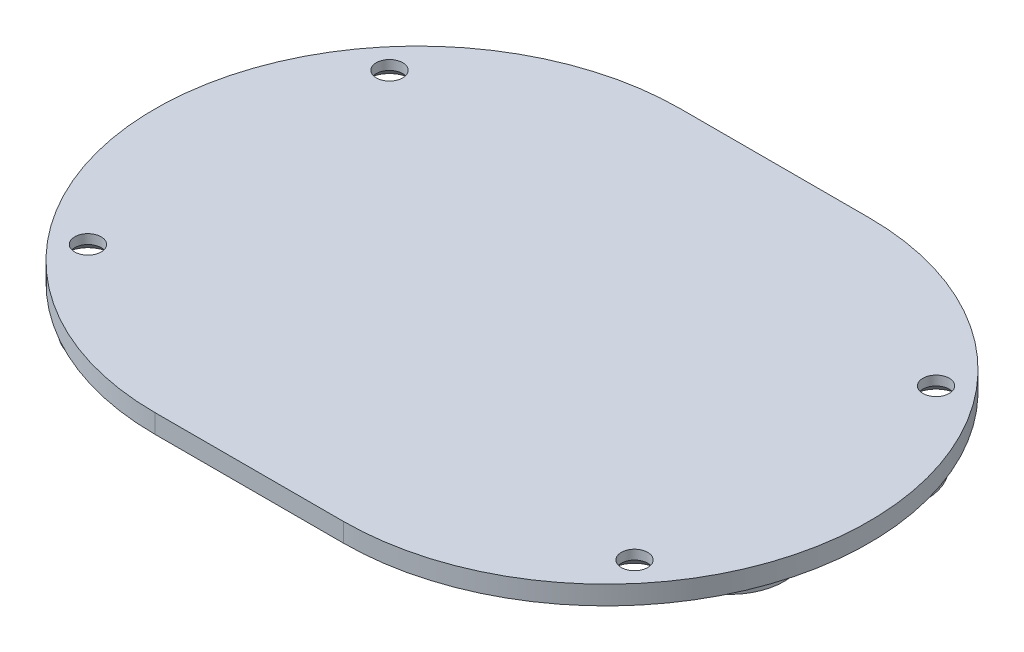
SolidWorks part; units mm, degrees
ref_plane "Front Plane" through (0, 0, 0) normal (0, 0, 1) x (1, 0, 0)
ref_plane "Top Plane" through (0, 0, 0) normal (0, 1, 0) x (1, 0, 0)
ref_plane "Right Plane" through (0, 0, 0) normal (1, 0, 0) x (0, 0, -1)
sketch "Sketch1" plane through (0, 2, 0) normal (0, -1, 0) x (1, 0, 0)
  line L0 (0, -27.9) -> (20, -27.9)
  line L1 (20, 27.9) -> (0, 27.9)
  line L4 (0, -28) -> (20, -28) construction
  line L5 (20, 28) -> (0, 28) construction
  arc A0 (20, -27.9) -> (20, 27.9) centre (20, 0) ccw
  arc A1 (0, 27.9) -> (0, -27.9) centre (0, 0) ccw
  arc A4 (0, 28) -> (0, -28) centre (0, 0) ccw construction
  arc A5 (20, -28) -> (20, 28) centre (20, 0) ccw construction
  dimension "D2" = 0.1
extrude "Boss-Extrude1" add sketch "Sketch1" along normal blind 2
hole_wizard "CSK for ST2.2 Cross recessed CTSK head tapping screws1" positions "Sketch2" profile "Sketch3" countersink size "ST2.2" standard "GB"
sketch "Sketch2" plane through (0, 0, 0) normal (0, -1, 0) x (-1, 0, 0)
  line L0 (0, 0) -> (-20, 0) construction
  line L3 (-39, 16) -> (19, 16)
  line L4 (-39, 16) -> (-39, -16)
  line L5 (-39, -16) -> (19, -16)
  line L6 (19, 16) -> (19, -16)
  line L7 (-10, 0) -> (-10, 22.0512) construction
  point P0 (-39, 16)
  point P2 (-39, -16)
  point P4 (19, -16)
  point P6 (19, 16)
  dimension "D1" = 32
  dimension "D2" = 58
sketch "Sketch3" plane through (39, 0, -16) normal (1, 0, 0) x (0, 0, -1)
  line L0 (0, 0) -> (0, 8.3412)
  line L1 (0, 8.3412) -> (1.4, 7.5)
  line L2 (1.4, 7.5) -> (1.4, 1)
  line L3 (1.4, 1) -> (2.4, 0)
  line L5 (2.4, 0) -> (0, 0)
  line L6 (-1.4, 1) -> (-2.4, 0) construction
  line L10 (0, 8.3412) -> (-1.4, 7.5) construction
  line L11 (0, -6.35) -> (0, 107.95) construction
  dimension "Hole Dia." = 2.8
  dimension "Hole Depth" = 7.5
  dimension "Near C'Sink Dia." = 4.8
  dimension "Near C'Sink Angle" = 90
  dimension "Drill Angle" = 118
sketch "Sketch4" plane through (0, 0, 0) normal (0, -1, 0) x (1, 0, 0)
  circle A0 centre (-11, 19.0526) radius 4.25
  circle A1 centre (-11, -19.0526) radius 4.25
  circle A2 centre (40.6732, 7.5244) radius 4.25
  circle A3 centre (40.6732, -7.5244) radius 4.25
  dimension "D1" = 8.5
extrude "Extrude-Thin1" add sketch "Sketch4" along normal blind 0.5 thin thin type one direction wall 1.5
